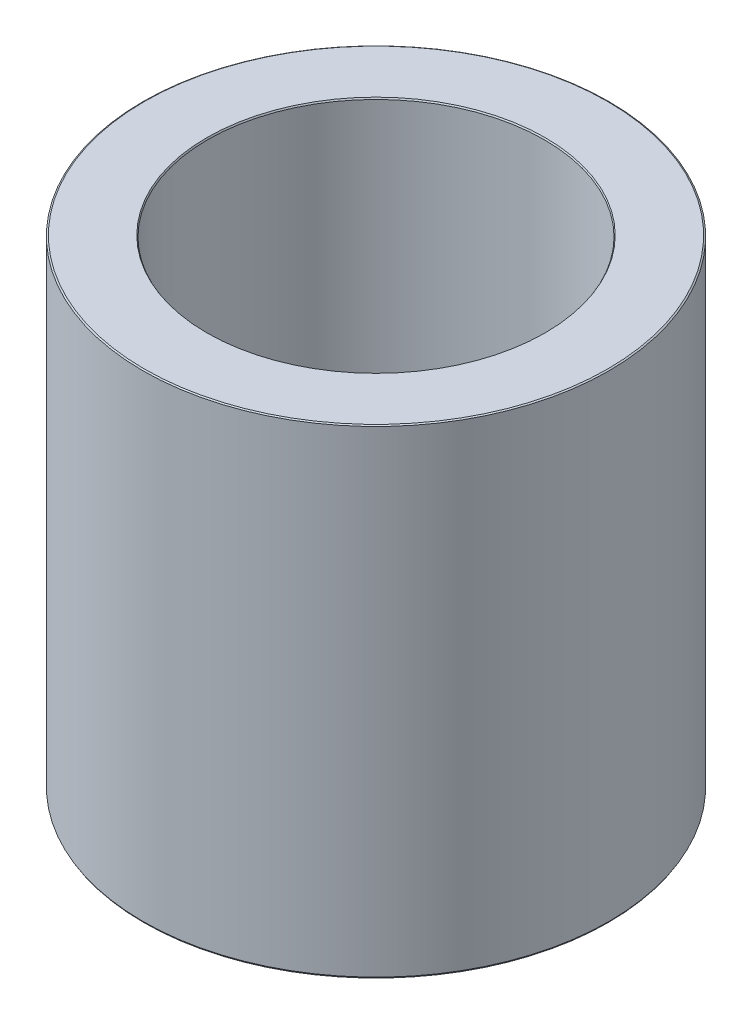
SolidWorks part; units mm, degrees
ref_plane "Front Plane" through (0, 0, 0) normal (0, 0, 1) x (1, 0, 0)
ref_plane "Top Plane" through (0, 0, 0) normal (0, 1, 0) x (1, 0, 0)
ref_plane "Right Plane" through (0, 0, 0) normal (1, 0, 0) x (0, 0, -1)
sketch "Sketch1" plane through (0, 0, 0) normal (0, 1, 0) x (1, 0, 0)
  circle A0 centre (0, 0) radius 60
  dimension "SLEEVE_OD" = 120
extrude "Boss-Extrude1" add sketch "Sketch1" along normal blind 123.3362
sketch "Sketch2" plane through (0, 0, 0) normal (0, 1, 0) x (1, 0, 0)
  circle A0 centre (0, 0) radius 43.3313
  dimension "BORE_D" = 86.6626
extrude "Cut-Extrude1" cut sketch "Sketch2" along normal through all
chamfer "Chamfer1" distance 0.2115 angle 60 4 edges at (0, 123.3362, 43.3313) (0, 0, 43.3313) (0, 0, 60) (0, 123.3362, 60) first distance on face at (0, 123.3362, 43.3313) first distance on face at (0, 0, 43.3313) first distance on face at (0, 123.3362, 60)
